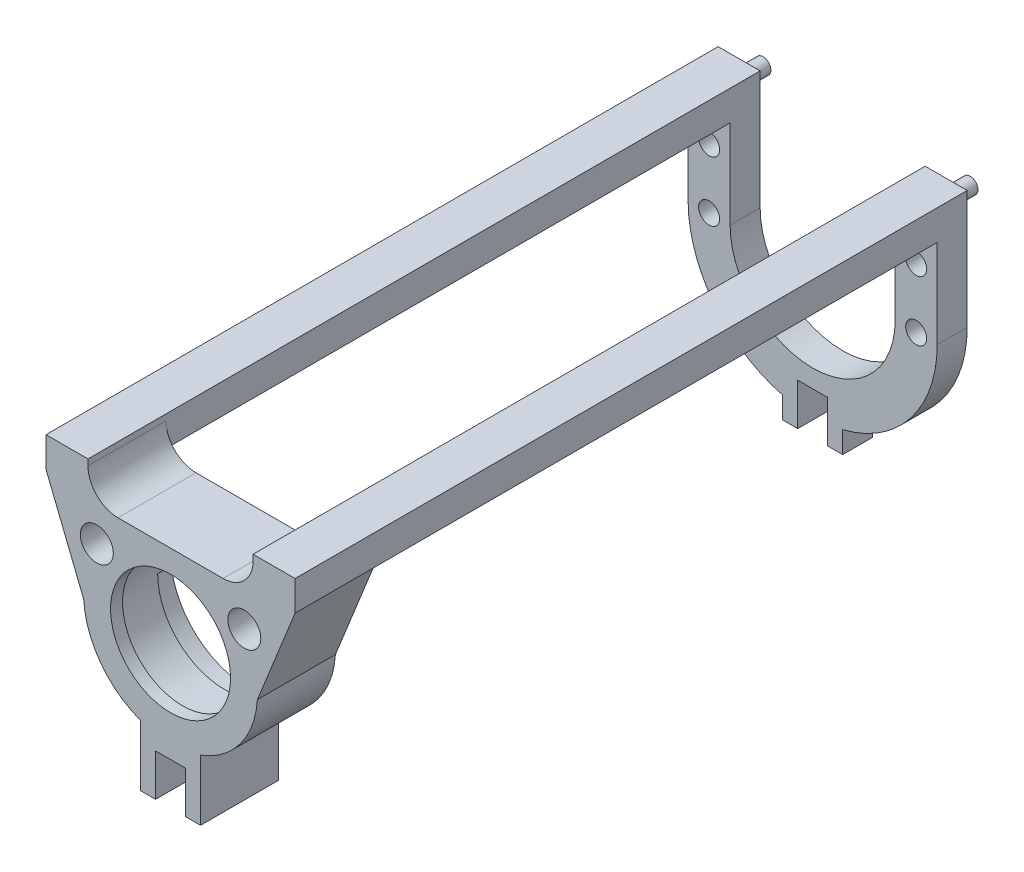
SolidWorks part; units mm, degrees
ref_plane "Front Plane" through (0, 0, 0) normal (0, 0, 1) x (1, 0, 0)
ref_plane "Top Plane" through (0, 0, 0) normal (0, 1, 0) x (1, 0, 0)
ref_plane "Right Plane" through (0, 0, 0) normal (1, 0, 0) x (0, 0, -1)
sketch "Sketch2" plane through (0, 0, 0) normal (0, 0, 1) x (1, 0, 0)
  line L13 (-2.5, -23.7532) -> (-2.5, -16.7532)
  line L14 (-2.5, -16.7532) -> (2.5, -16.7532)
  line L15 (2.5, -16.7532) -> (2.5, -23.7532)
  line L16 (2.5, -23.7532) -> (5, -23.7532)
  line L17 (5, -23.7532) -> (5, -20.1419)
  line L18 (20.7532, 0) -> (20.7532, 19.75)
  line L19 (20.7532, 19.75) -> (13.7532, 19.75)
  line L20 (13.7532, 19.75) -> (13.7532, 0)
  line L21 (-13.7532, 0) -> (-13.7532, 19.75)
  line L22 (-13.7532, 19.75) -> (-20.7532, 19.75)
  line L23 (-20.7532, 19.75) -> (-20.7532, 0)
  line L24 (-5, -20.1419) -> (-5, -23.7532)
  line L25 (-5, -23.7532) -> (-2.5, -23.7532)
  line L26 (-2.5, -23.7532) -> (-2.5, -16.7532)
  line L27 (-2.5, -16.7532) -> (2.5, -16.7532)
  line L28 (2.5, -16.7532) -> (2.5, -23.7532)
  line L29 (2.5, -23.7532) -> (5, -23.7532)
  line L30 (5, -23.7532) -> (5, -20.1419)
  line L31 (20.7532, 0) -> (20.7532, 19.75)
  line L32 (20.7532, 19.75) -> (13.7532, 19.75)
  line L33 (13.7532, 19.75) -> (13.7532, 0)
  line L34 (-13.7532, 0) -> (-13.7532, 19.75)
  line L35 (-13.7532, 19.75) -> (-20.7532, 19.75)
  line L36 (-20.7532, 19.75) -> (-20.7532, 0)
  line L37 (-5, -20.1419) -> (-5, -23.7532)
  line L38 (-5, -23.7532) -> (-2.5, -23.7532)
  circle A0 centre (17.2532, 10) radius 1.75 construction
  circle A1 centre (17.2532, 0) radius 1.75 construction
  circle A2 centre (-17.2532, 0) radius 1.75 construction
  arc A3 (5, -20.1419) -> (20.7532, 0) centre (0, 0) ccw
  arc A4 (-13.7532, 0) -> (13.7532, 0) centre (0, 0) ccw
  arc A5 (-20.7532, 0) -> (-5, -20.1419) centre (0, 0) ccw
  arc A6 (5, -20.1419) -> (20.7532, 0) centre (0, 0) ccw
  arc A7 (-13.7532, 0) -> (13.7532, 0) centre (0, 0) ccw
  arc A8 (-20.7532, 0) -> (-5, -20.1419) centre (0, 0) ccw
  circle A9 centre (-17.2532, 10) radius 1.75 construction
  circle A10 centre (17.2532, 10) radius 1.75
  circle A11 centre (17.2532, 0) radius 1.75
  circle A12 centre (-17.2532, 0) radius 1.75
  circle A13 centre (-17.2532, 10) radius 1.75
  dimension "D1" = 0
extrude "Boss-Extrude1" add sketch "Sketch2" along normal blind 5
sketch "Sketch3" plane through (0, 0, 0) normal (0, 0, -1) x (-1, 0, 0)
  circle A0 centre (17.2532, 16.75) radius 1.3
  circle A1 centre (-17.2532, 16.75) radius 1.3
  dimension "D1" = 2.6
  dimension "D2" = 2.6
extrude "Boss-Extrude2" add sketch "Sketch3" along normal blind 4
sketch "Sketch4" plane through (0, 0, 5) normal (0, 0, 1) x (1, 0, 0)
  line L0 (-13.7532, 0) -> (-13.7532, 19.75) construction
  line L1 (-20.7532, 19.75) -> (-13.7532, 19.75)
  line L2 (-20.7532, 19.75) -> (-20.7532, 14.75)
  line L3 (-20.7532, 14.75) -> (-13.7532, 14.75)
  line L4 (-13.7532, 19.75) -> (-13.7532, 14.75)
  line L5 (20.7532, 0) -> (20.7532, 19.75) construction
  line L6 (13.7532, 19.75) -> (20.7532, 19.75)
  line L7 (13.7532, 19.75) -> (13.7532, 14.75)
  line L8 (13.7532, 14.75) -> (20.7532, 14.75)
  line L9 (20.7532, 19.75) -> (20.7532, 14.75)
  dimension "D1" = 5
  dimension "D2" = 5
extrude "Boss-Extrude3" add sketch "Sketch4" along normal up to surface (107 mm away)
sketch "Sketch5" plane through (0, 0, 112) normal (0, 0, 1) x (1, 0, 0)
  line L0 (-13.7532, 19.75) -> (-13.7532, 0)
  line L1 (13.7532, 0) -> (13.7532, 19.75)
  line L2 (13.7532, 19.75) -> (20.7532, 19.75)
  line L8 (-20.7532, 19.75) -> (-13.7532, 19.75)
  line L9 (0, 13.7532) -> (-13.7532, 13.7532)
  line L10 (-13.7532, 13.7532) -> (13.7532, 13.7532)
  line L11 (20.7532, 19.75) -> (20.7532, 14.75)
  line L12 (-20.7532, 19.75) -> (-20.7532, 14.75)
  line L13 (-12.7605, -5.1303) -> (-20.7532, 14.75)
  line L14 (12.7605, -5.1303) -> (20.7532, 14.75)
  circle A0 centre (0, 0) radius 10
  circle A1 centre (0, 0) radius 13.7532
  line M11 (20.7532, 19.75) -> (13.7532, 19.75)
  line M12 (13.7532, 19.75) -> (13.7532, 14.75)
  line M13 (13.7532, 14.75) -> (20.7532, 14.75)
  line M14 (20.7532, 14.75) -> (20.7532, 19.75)
  dimension "D1" = 20
extrude "Boss-Extrude4" add sketch "Sketch5" against normal blind 2 contours A1 L9 L0 | A1 A0 | A1 L14 L1 M13 | M14 M11 M12 M13 | A1 L1 L10 | A1 L0 L8 L12 L13 region at (-16.4984, 11.9079, 112) region at (-10.6812, 10.6812, 112) region at (-9.4499, 9.4499, 112) region at (10.6812, 10.6812, 112) region at (16.0681, 8.8621, 112) region at (17.2532, 17.25, 112)
sketch "Sketch6" plane through (0, 0, 110) normal (0, 0, -1) x (-1, 0, 0)
  line L7 (12.7605, -5.1303) -> (20.7532, 14.75)
  line L8 (20.7532, 14.75) -> (13.7532, 14.75)
  line L9 (13.7532, 14.75) -> (13.7532, 13.7532)
  line L10 (13.7532, 13.7532) -> (-13.7532, 13.7532)
  line L11 (-13.7532, 13.7532) -> (-13.7532, 14.75)
  line L12 (-13.7532, 14.75) -> (-20.7532, 14.75)
  line L13 (-20.7532, 14.75) -> (-12.7605, -5.1303)
  line L14 (12.7605, -5.1303) -> (20.7532, 14.75)
  line L15 (20.7532, 14.75) -> (13.7532, 14.75)
  line L16 (13.7532, 14.75) -> (13.7532, 13.7532)
  line L17 (13.7532, 13.7532) -> (-13.7532, 13.7532)
  line L18 (-13.7532, 13.7532) -> (-13.7532, 14.75)
  line L19 (-13.7532, 14.75) -> (-20.7532, 14.75)
  line L20 (-20.7532, 14.75) -> (-12.7605, -5.1303)
  circle A0 centre (0, 0) radius 11.15
  circle A1 centre (0, 0) radius 13.7532
  arc A3 (-12.7605, -5.1303) -> (12.7605, -5.1303) centre (0, 0) ccw
  arc A4 (-12.7605, -5.1303) -> (12.7605, -5.1303) centre (0, 0) ccw
  line M12 (12.7605, -5.1303) -> (20.7532, 14.75)
  line M13 (20.7532, 14.75) -> (13.7532, 14.75)
  line M14 (13.7532, 14.75) -> (13.7532, 13.7532)
  line M15 (13.7532, 13.7532) -> (-13.7532, 13.7532)
  line M16 (-13.7532, 13.7532) -> (-13.7532, 14.75)
  line M17 (-13.7532, 14.75) -> (-20.7532, 14.75)
  line M18 (-20.7532, 14.75) -> (-12.7605, -5.1303)
  arc M19 (-12.7605, -5.1303) -> (12.7605, -5.1303) centre (0, 0) ccw
  dimension "D1" = 22.3
  dimension "D2" = 0
extrude "Boss-Extrude5" add sketch "Sketch6" along normal blind 10 contours A1 M12 M13 M14 M15 | A1 L17 M16 M17 M18 | A1 A0 M19 region at (-13.9238, 9.5862, 110) region at (0, -13.3642, 110) region at (13.9238, 9.5862, 110)
sketch "Sketch7" plane through (0, 0, 100) normal (0, 0, -1) x (-1, 0, 0)
  circle A0 centre (0, 0) radius 13
  dimension "D1" = 26
extrude "Cut-Extrude1" cut sketch "Sketch7" against normal up to surface (3 mm away)
sketch "Sketch8" plane through (0, 0, 103) normal (0, 0, -1) x (-1, 0, 0)
  line L0 (0, 0) -> (13, 0)
  line L1 (13, 0) -> (-13, 0)
  line L2 (0, 0) -> (12.5532, 5.8537)
  line L3 (0, 0) -> (-13.2945, -6.1993)
  circle A0 centre (0, 0) radius 13
  circle A1 centre (0, 0) radius 11.15
  circle M6 centre (0, 0) radius 11.15
  circle M7 centre (0, 0) radius 13
  dimension "D1" = 25
  dimension "D2" = 25
extrude "Boss-Extrude6" add sketch "Sketch8" along normal up to surface (3 mm away) contours L2 L0 M6 M7 | L3 L1 M6 M7 region at (-11.7184, 2.5979, 103) region at (11.7184, -2.5979, 103) up to face at (-13, 0, 100)
sketch "Sketch9" plane through (0, 0, 100) normal (0, 0, -1) x (-1, 0, 0)
  line L0 (-11.15, 0) -> (-13, 0) construction
  line L1 (-10.1053, -4.7122) -> (-11.782, -5.494) construction
  line L2 (11.15, 0) -> (13, 0) construction
  line L3 (10.1053, 4.7122) -> (11.782, 5.494) construction
  line L4 (-11.15, 0) -> (-13, 0)
  line L5 (-10.1053, -4.7122) -> (-11.782, -5.494)
  line L6 (11.15, 0) -> (13, 0)
  line L7 (13.7532, 13.7532) -> (-13.7532, 13.7532)
  line L8 (-13.7532, 13.7532) -> (-13.7532, 14.75)
  line L9 (-13.7532, 14.75) -> (-20.7532, 14.75)
  line L10 (-20.7532, 14.75) -> (-12.7605, -5.1303)
  line L11 (12.7605, -5.1303) -> (20.7532, 14.75)
  line L12 (20.7532, 14.75) -> (13.7532, 14.75)
  line L13 (13.7532, 14.75) -> (13.7532, 13.7532)
  line L14 (13.7532, 13.7532) -> (-13.7532, 13.7532)
  line L15 (-13.7532, 13.7532) -> (-13.7532, 14.75)
  line L16 (-13.7532, 14.75) -> (-20.7532, 14.75)
  line L17 (-20.7532, 14.75) -> (-12.7605, -5.1303)
  line L18 (12.7605, -5.1303) -> (20.7532, 14.75)
  line L19 (20.7532, 14.75) -> (13.7532, 14.75)
  line L20 (13.7532, 14.75) -> (13.7532, 13.7532)
  line L21 (10.1053, 4.7122) -> (11.782, 5.494)
  arc A0 (-11.15, 0) -> (-10.1053, -4.7122) centre (0, 0) ccw construction
  arc A1 (-12.7605, -5.1303) -> (12.7605, -5.1303) centre (0, 0) ccw
  arc A2 (-12.7605, -5.1303) -> (12.7605, -5.1303) centre (0, 0) ccw
  arc A3 (-11.782, -5.494) -> (13, 0) centre (0, 0) ccw construction
  arc A4 (11.15, 0) -> (10.1053, 4.7122) centre (0, 0) ccw construction
  arc A5 (11.782, 5.494) -> (-13, 0) centre (0, 0) ccw construction
  arc A6 (-11.15, 0) -> (-10.1053, -4.7122) centre (0, 0) ccw
  arc A7 (-11.782, -5.494) -> (13, 0) centre (0, 0) ccw
  arc A8 (11.15, 0) -> (10.1053, 4.7122) centre (0, 0) ccw
  arc A9 (11.782, 5.494) -> (-13, 0) centre (0, 0) ccw
  dimension "D1" = 0
extrude "Boss-Extrude7" add sketch "Sketch9" along normal blind 1
sketch "Sketch10" plane through (0, 0, 99) normal (0, 0, -1) x (-1, 0, 0)
  line L0 (0, 0) -> (0, 13)
  line L1 (0, 13) -> (0, -13)
  circle A0 centre (0, 0) radius 13
  circle A1 centre (0, 0) radius 11.15
  line M9 (-11.782, -5.494) -> (-10.1053, -4.7122)
  arc M12 (-13, 0) -> (11.782, 5.494) centre (0, 0) cw
  line M13 (11.782, 5.494) -> (10.1053, 4.7122)
  arc M16 (13, 0) -> (-11.782, -5.494) centre (0, 0) cw
extrude "Boss-Extrude8" add sketch "Sketch10" against normal blind 2 contours A1 L1 M13 M12 | A1 L1 M9 M16 region at (-6.1576, 9.6654, 99) region at (6.1576, -9.6654, 99)
fillet "Fillet1" radius 5 2 edges at (0, -12.075, 101) (0, 12.075, 101)
sketch "Sketch11" plane through (0, 0, 112) normal (0, 0, 1) x (1, 0, 0)
  line L0 (2.5, -16.7532) -> (2.5, -23.7532) construction
  line L1 (-2.5, -16.7532) -> (2.5, -16.7532) construction
  line L2 (-2.5, -23.7532) -> (-2.5, -16.7532) construction
  line L3 (2.5, -16.7532) -> (2.5, -23.7532)
  line L4 (-2.5, -16.7532) -> (2.5, -16.7532)
  line L5 (-2.5, -23.7532) -> (-2.5, -16.7532)
  line L6 (2.5, -23.7532) -> (5, -23.7532)
  line L7 (5, -23.7532) -> (5, -12.8121)
  line L8 (-2.5, -23.7532) -> (-5, -23.7532)
  line L9 (-5, -23.7532) -> (-5, -12.8121)
  arc A0 (-12.7605, -5.1303) -> (12.7605, -5.1303) centre (0, 0) ccw construction
  arc A1 (-5, -12.8121) -> (5, -12.8121) centre (0, 0) ccw
extrude "Boss-Extrude9" add sketch "Sketch11" against normal up to surface (13 mm away) up to face at (0, 0, 99)
fillet "Fillet3" radius 5 2 edges at (13.7532, 13.7532, 105.5) (-13.7532, 13.7532, 105.5)
sketch "Sketch13" plane through (0, 0, 112) normal (0, 0, 1) x (1, 0, 0)
  line L0 (-12.2887, 15.2177) -> (-12.2887, 8.2177)
  line L1 (0, 13.7532) -> (0, 16.2472)
  line L2 (8.7532, 13.7532) -> (-8.7532, 13.7532) construction
  arc A0 (-13.7532, 18.7532) -> (-8.7532, 13.7532) centre (-8.7532, 18.7532) ccw construction
  circle A1 centre (-12.2887, 8.2177) radius 2.75
  circle A2 centre (12.2887, 8.2177) radius 2.75
  dimension "D2" = 5.5
  dimension "D1" = 7
extrude "Cut-Extrude2" cut sketch "Sketch13" against normal blind 15 contours A1 | A2 region at (-14.1783, 6.3281, 112) region at (12.2887, 8.2177, 112)
sketch "Sketch14" plane through (0, 0, 99) normal (0, 0, -1) x (-1, 0, 0)
  line L0 (-20.7532, 14.75) -> (-12.7605, -5.1303)
  line L1 (12.7605, -5.1303) -> (20.7532, 14.75)
  circle A0 centre (0, 0) radius 13.7532
  circle A1 centre (0, 0) radius 14.5
  arc M21 (-12.7605, -5.1303) -> (-5, -12.8121) centre (0, 0) ccw
  line M22 (-5, -12.8121) -> (-5, -23.7532)
  line M28 (5, -23.7532) -> (5, -12.8121)
  arc M29 (5, -12.8121) -> (12.7605, -5.1303) centre (0, 0) ccw
  line M30 (12.7605, -5.1303) -> (20.7532, 14.75)
  dimension "D1" = 29
extrude "Boss-Extrude10" add sketch "Sketch14" against normal up to surface (13 mm away) contours A1 M28 M30 M29 | A1 A0 M22 M28 | L0 A1 M22 M21 region at (13.7646, -3.0585, 99) region at (0, -13.8202, 99) region at (-11.5087, -8.5568, 99) up to face at (15.0387, 8.2177, 112)
